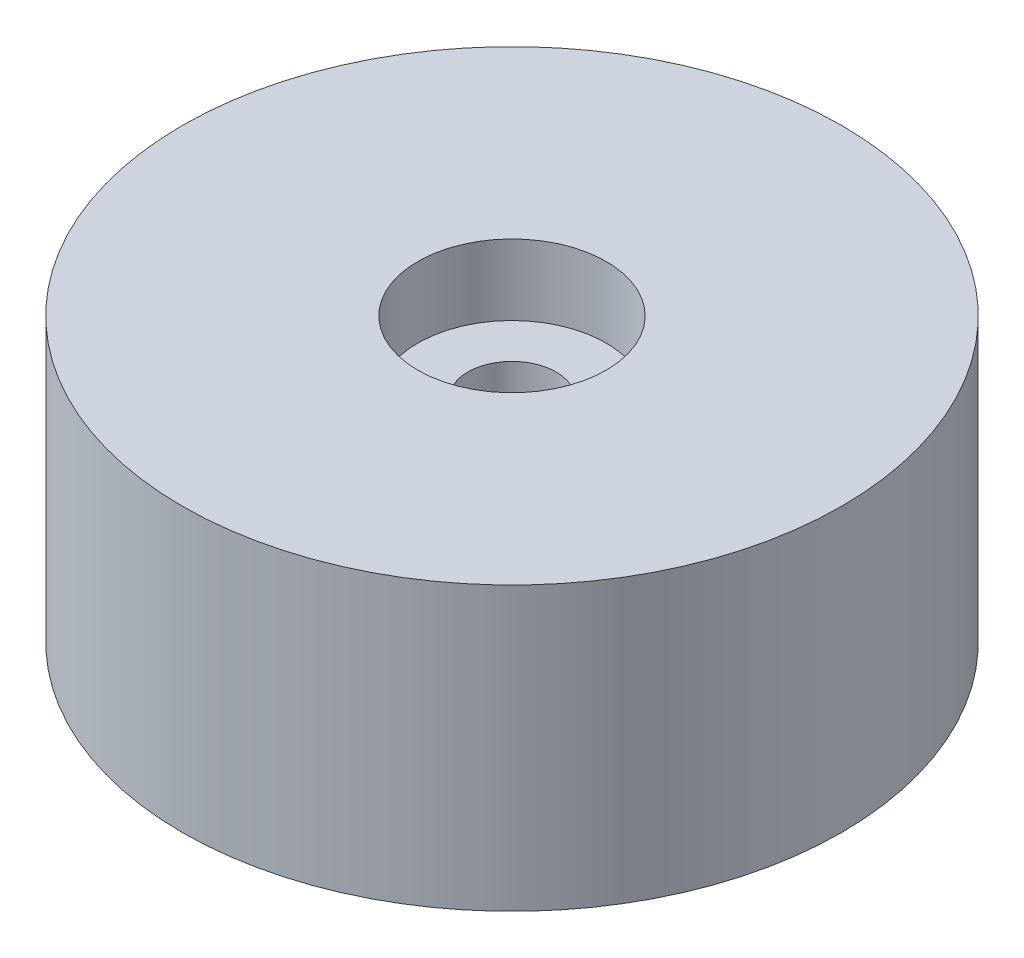
SolidWorks part; units mm, degrees
ref_plane "前视基准面" through (0, 0, 0) normal (0, 0, 1) x (1, 0, 0)
ref_plane "上视基准面" through (0, 0, 0) normal (0, 1, 0) x (1, 0, 0)
ref_plane "右视基准面" through (0, 0, 0) normal (1, 0, 0) x (0, 0, -1)
other "Configuration Table"
sketch "草图1" plane through (0, 0, 0) normal (0, 1, 0) x (1, 0, 0)
  circle A0 centre (0, 0) radius 5.6
  dimension "D2" = 11.2
extrude "凸台-拉伸1" add sketch "草图1" along normal blind 4.8 contours A0
sketch "草图2" plane through (0, 4.8, 0) normal (0, 1, 0) x (1, 0, 0)
  circle A0 centre (0, 0) radius 1.6
  circle A1 centre (0, 0) radius 0.75
  dimension "D1" = 3.2
  dimension "D2" = 1.5
extrude "切除-拉伸1" cut sketch "草图2" against normal through all contours A1
extrude "切除-拉伸2" cut sketch "草图2<3>" against normal blind 1.2 contours A0
sketch "草图2<3>" plane through (0, 4.8, 0) normal (0, 1, 0) x (1, 0, 0) same geometry as "草图2"
extrude "切除-拉伸3" cut sketch "草图2<4>" along normal blind 1.2 from surface contours A0 starting at face at (0, 0, 0.75)
sketch "草图2<4>" plane through (0, 4.8, 0) normal (0, 1, 0) x (1, 0, 0) same geometry as "草图2"
